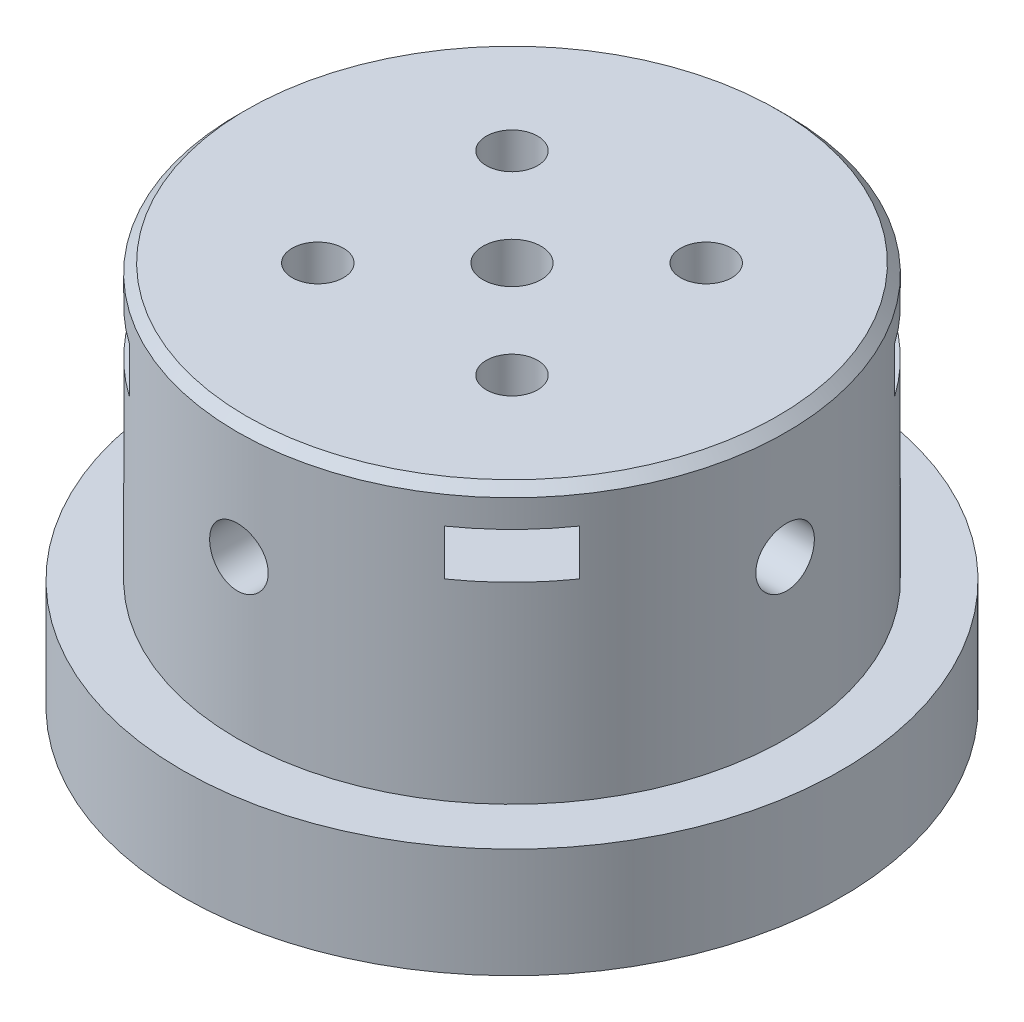
SolidWorks part; units mm, degrees
ref_plane "Front Plane" through (0, 0, 0) normal (0, 0, 1) x (1, 0, 0)
ref_plane "Top Plane" through (0, 0, 0) normal (0, 1, 0) x (1, 0, 0)
ref_plane "Right Plane" through (0, 0, 0) normal (1, 0, 0) x (0, 0, -1)
sketch "Sketch1" plane through (0, 0, 0) normal (0, 1, 0) x (1, 0, 0)
  circle A0 centre (0, 0) radius 15
  dimension "D1" = 30
extrude "Boss-Extrude1" add sketch "Sketch1" along normal blind 2
sketch "Sketch2" plane through (0, 2, 0) normal (0, 1, 0) x (1, 0, 0)
  circle A0 centre (0, 0) radius 13.5
  circle A1 centre (0, 0) radius 15
  circle A2 centre (0, 0) radius 15
  dimension "D1" = 0
  dimension "D2" = 1.5
extrude "Boss-Extrude2" add sketch "Sketch2" against normal up to surface (15 mm away)
sketch "Sketch3" plane through (0, -13, 0) normal (0, -1, 0) x (1, 0, 0)
  circle A0 centre (0, 0) radius 13.5 construction
  circle A1 centre (0, 0) radius 13.5
  circle A2 centre (0, 0) radius 18
  dimension "D1" = 36
extrude "Boss-Extrude3" add sketch "Sketch3" along normal up to surface (2 mm away)
sketch "Sketch4" plane through (0, -15, 0) normal (0, -1, 0) x (1, 0, 0)
  circle A0 centre (0, 0) radius 16.1
  circle A1 centre (0, 0) radius 18
  circle A2 centre (0, 0) radius 18
  dimension "D2" = 32.2
  dimension "D1" = 0
extrude "Boss-Extrude4" add sketch "Sketch4" along normal up to surface (3.9878 mm away)
chamfer "Chamfer1" distance 1 angle 45 1 edges at (0, -15, 13.5)
sketch "Sketch5" plane through (0, 2, 0) normal (0, 1, 0) x (1, 0, 0)
  circle A0 centre (0, 0) radius 13.5
  circle A1 centre (0, 0) radius 13.5 construction
extrude "Boss-Extrude5" add sketch "Sketch5" against normal up to surface (10.8216 mm away)
sketch "Sketch6" plane through (0, 2, 0) normal (0, 1, 0) x (1, 0, 0)
  circle A0 centre (0, 0) radius 1.5875
  dimension "D1" = 3.175
extrude "Cut-Extrude1" cut sketch "Sketch6" against normal through all both and the other way through all
sketch "Sketch7" plane through (0, 0, 0) normal (1, 0, 0) x (0, 0, -1)
  line L0 (0, 0) -> (0, -8.8216) construction
  line L1 (-1.5875, -8.8216) -> (1.5875, -8.8216) construction
  circle A0 centre (0, -4.4108) radius 1.6
  dimension "D1" = 3.2
extrude "Cut-Extrude2" cut sketch "Sketch7" against normal through all
ref_axis "Axis1" through (0, -14, 0) along (0, 1, 0)
ref_plane "Plane2" through (-10, 0, 0) normal (1, 0, 0) x (0, 0, -1)
ref_plane "Plane3" through (-9, 0, 0) normal (1, 0, 0) x (0, 0, -1)
sketch "Sketch11" plane through (-10, 0, 0) normal (1, 0, 0) x (0, 0, -1)
  circle A0 centre (0, -4.4108) radius 1.6 construction
  circle A1 centre (0, -4.4108) radius 1.6 construction
  circle A2 centre (0, -4.4108) radius 2
  dimension "D1" = 4
extrude "Cut-Extrude7" [suppressed] cut sketch "Sketch11" along normal blind 5.5
sketch "Sketch12" plane through (-10, 0, 0) normal (1, 0, 0) x (0, 0, -1)
  circle A0 centre (0, -4.4108) radius 3.5
  dimension "D1" = 7
extrude "Cut-Extrude8" [suppressed] cut sketch "Sketch12" against normal blind 5
chamfer "Chamfer2" [suppressed] distance 1 angle 45
pattern_circular "CirPattern3" count 4 over 360 about axis through (0, -14, 0) along (0, 1, 0) of "Cut-Extrude2", "Cut-Extrude7", "Cut-Extrude8", "Chamfer2"
sketch "Sketch13" plane through (-9, 0, 0) normal (1, 0, 0) x (0, 0, -1)
  line L0 (-2.75, -5.9985) -> (-2.75, -8.8216)
  line L1 (0, -7.5862) -> (2.75, -5.9985) construction
  line L2 (2.75, -5.9985) -> (2.75, -2.8231)
  line L3 (2.75, -2.8231) -> (0, -1.2354)
  line L4 (0, -1.2354) -> (-2.75, -2.8231)
  line L5 (-2.75, -2.8231) -> (-2.75, -5.9985)
  line L6 (-2.75, -5.9985) -> (0, -7.5862) construction
  line L7 (-2.75, -8.8216) -> (2.75, -8.8216)
  line L8 (2.75, -8.8216) -> (2.75, -5.9985)
  line L9 (-1.5875, -8.8216) -> (1.5875, -8.8216) construction
  circle A0 centre (0, -4.4108) radius 2.75 construction
  circle A1 centre (0, -4.4108) radius 1.6 construction
  dimension "D1" = 5.5
extrude "Cut-Extrude9" cut sketch "Sketch13" along normal blind 3
pattern_circular "CirPattern4" count 4 over 360 about axis through (0, -14, 0) along (0, 1, 0) of "Cut-Extrude9"
sketch "Sketch14" plane through (0, 2, 0) normal (0, -1, 0) x (1, 0, 0)
  line L0 (0, 0) -> (0, 13.5) construction
  line L1 (0, 0) -> (-9.5459, 9.5459) construction
  circle A0 centre (0, 0) radius 13.5 construction
  circle A1 centre (-5.3033, 5.3033) radius 1.4
  circle A2 centre (5.3033, 5.3033) radius 1.4
  circle A3 centre (5.3033, -5.3033) radius 1.4
  circle A4 centre (-5.3033, -5.3033) radius 1.4
  point P18 (0, 0)
  dimension "D3" = 2.8
  dimension "D1" = 45
  dimension "D2" = 7.5
  dimension "D4" = 4
extrude "Cut-Extrude10" cut sketch "Sketch14" along normal blind 4.5 and the other way through all
ref_plane "Plane4" through (0, 0, 0) normal (0, 1, 0) x (1, 0, 0)
sketch "Sketch15" plane through (0, 0, 0) normal (0, 1, 0) x (1, 0, 0)
  line L0 (0, 0) -> (-10.6066, 10.6066) construction
  line L1 (-8.2032, 4.5263) -> (-12.4451, 8.7681)
  line L2 (-7.4262, 7.4262) -> (-8.2032, 4.5263) construction
  line L3 (-8.2032, 4.5263) -> (-6.0803, 2.4034)
  line L4 (-6.0803, 2.4034) -> (-3.1804, 3.1804)
  line L5 (-3.1804, 3.1804) -> (-2.4034, 6.0803)
  line L6 (-2.4034, 6.0803) -> (-4.5263, 8.2032)
  line L7 (-4.5263, 8.2032) -> (-7.4262, 7.4262) construction
  line L8 (-12.4451, 8.7681) -> (-8.7681, 12.4451)
  line L9 (-8.7681, 12.4451) -> (-4.5263, 8.2032)
  line L10 (12.4451, 8.7681) -> (8.2032, 4.5263)
  line L11 (6.0803, 2.4034) -> (8.2032, 4.5263)
  line L12 (3.1804, 3.1804) -> (6.0803, 2.4034)
  line L13 (2.4034, 6.0803) -> (3.1804, 3.1804)
  line L14 (4.5263, 8.2032) -> (2.4034, 6.0803)
  line L15 (4.5263, 8.2032) -> (8.7681, 12.4451)
  line L16 (8.7681, 12.4451) -> (12.4451, 8.7681)
  line L17 (8.7681, -12.4451) -> (4.5263, -8.2032)
  line L18 (2.4034, -6.0803) -> (4.5263, -8.2032)
  line L19 (3.1804, -3.1804) -> (2.4034, -6.0803)
  line L20 (6.0803, -2.4034) -> (3.1804, -3.1804)
  line L21 (8.2032, -4.5263) -> (6.0803, -2.4034)
  line L22 (8.2032, -4.5263) -> (12.4451, -8.7681)
  line L23 (12.4451, -8.7681) -> (8.7681, -12.4451)
  line L24 (-12.4451, -8.7681) -> (-8.2032, -4.5263)
  line L25 (-6.0803, -2.4034) -> (-8.2032, -4.5263)
  line L26 (-3.1804, -3.1804) -> (-6.0803, -2.4034)
  line L27 (-2.4034, -6.0803) -> (-3.1804, -3.1804)
  line L28 (-4.5263, -8.2032) -> (-2.4034, -6.0803)
  line L29 (-4.5263, -8.2032) -> (-8.7681, -12.4451)
  line L30 (-8.7681, -12.4451) -> (-12.4451, -8.7681)
  circle A0 centre (0, 0) radius 15 construction
  circle A1 centre (-5.3033, 5.3033) radius 2.6 construction
  point P5 (-5.3033, 5.3033)
  point P41 (0, 0)
  dimension "D1" = 5.2
  dimension "D2" = 4
extrude "Cut-Extrude11" cut sketch "Sketch15" against normal blind 2.5
chamfer "Chamfer3" distance 0.5 angle 45 1 edges at (0, 2, 15)
